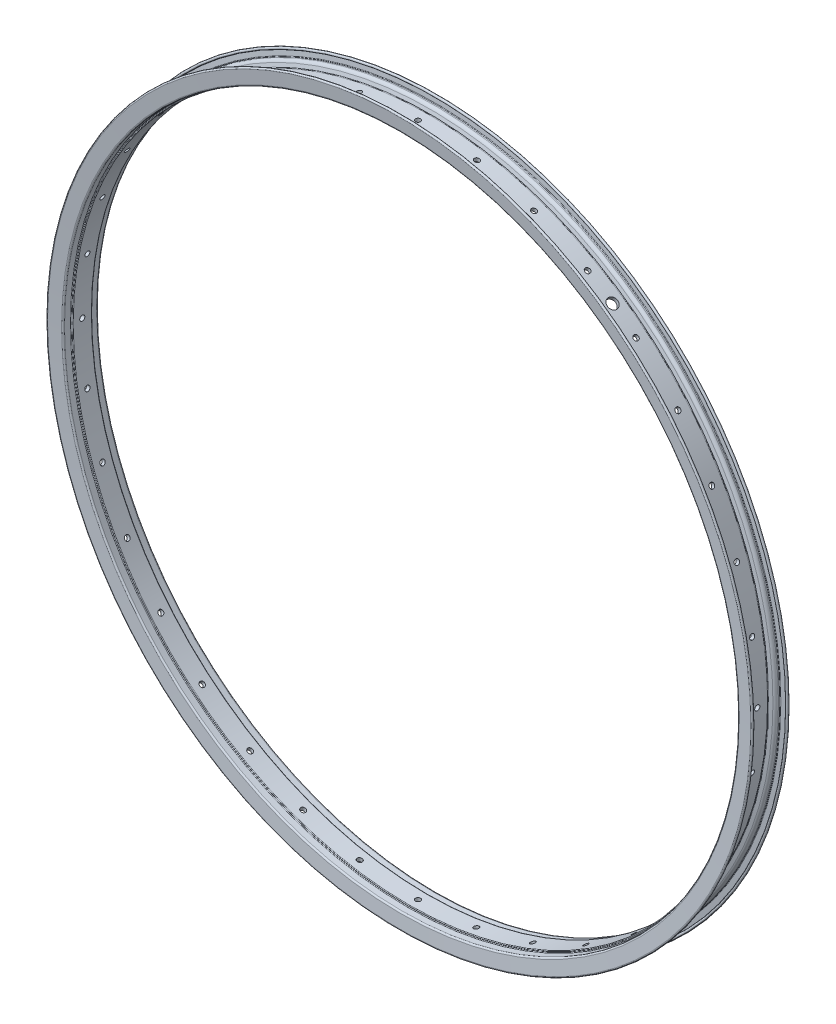
SolidWorks part; units mm, degrees
ref_plane "Alzado" through (0, 0, 0) normal (0, 0, 1) x (1, 0, 0)
ref_plane "Planta" through (0, 0, 0) normal (0, 1, 0) x (1, 0, 0)
ref_plane "Vista lateral" through (0, 0, 0) normal (1, 0, 0) x (0, 0, -1)
sketch "Croquis1" plane through (0, 0, 0) normal (1, 0, 0) x (0, 0, -1)
  line L0 (-255.6246, 0) -> (255.6246, 0) construction
  line L1 (0, 318.7713) -> (0, -318.7713) construction
  line L2 (7.3596, 274) -> (-7.3596, 274)
  line L3 (-7.8447, 274.6213) -> (-7.8053, 274.7787)
  line L4 (-8.2904, 275.4) -> (-13.1129, 275.4)
  line L5 (-14.3573, 276.5321) -> (-15.35, 287.0056)
  line L6 (-14.2601, 286.1045) -> (-13.8972, 282.2761)
  line L7 (-13.3995, 281.8233) -> (-12.3995, 281.8233)
  line L8 (-9.7847, 279.9251) -> (-8.9124, 277.2476)
  line L9 (-8.437, 276.9024) -> (8.437, 276.9024)
  line L10 (9.7847, 279.9251) -> (8.9124, 277.2476)
  line L11 (13.3995, 281.8233) -> (12.3995, 281.8233)
  line L12 (14.2601, 286.1045) -> (13.8972, 282.2761)
  line L13 (14.3573, 276.5321) -> (15.35, 287.0056)
  line L14 (8.2904, 275.4) -> (13.1129, 275.4)
  line L15 (7.8447, 274.6213) -> (7.8053, 274.7787)
  arc A1 (-14.2601, 286.1045) -> (-15.35, 287.0056) centre (-14.3545, 287.1) ccw
  arc A2 (-7.8053, 274.7787) -> (-8.2904, 275.4) centre (-8.2904, 274.9) ccw
  arc A3 (-7.8447, 274.6213) -> (-7.3596, 274) centre (-7.3596, 274.5) ccw
  arc A4 (-14.3573, 276.5321) -> (-13.1129, 275.4) centre (-13.1129, 276.65) ccw
  arc A5 (-9.7847, 279.9251) -> (-12.3995, 281.8233) centre (-12.3995, 279.0733) ccw
  arc A6 (-8.437, 276.9024) -> (-8.9124, 277.2476) centre (-8.437, 277.4024) cw
  arc A7 (-13.8972, 282.2761) -> (-13.3995, 281.8233) centre (-13.3995, 282.3233) ccw
  arc A8 (13.8972, 282.2761) -> (13.3995, 281.8233) centre (13.3995, 282.3233) cw
  arc A9 (8.437, 276.9024) -> (8.9124, 277.2476) centre (8.437, 277.4024) ccw
  arc A10 (9.7847, 279.9251) -> (12.3995, 281.8233) centre (12.3995, 279.0733) cw
  arc A11 (14.3573, 276.5321) -> (13.1129, 275.4) centre (13.1129, 276.65) cw
  arc A12 (7.8447, 274.6213) -> (7.3596, 274) centre (7.3596, 274.5) cw
  arc A13 (7.8053, 274.7787) -> (8.2904, 275.4) centre (8.2904, 274.9) cw
  arc A14 (14.2601, 286.1045) -> (15.35, 287.0056) centre (14.3545, 287.1) cw
  point P4 (0, 0)
  point P8 (0, 0)
  point P20 (-7.65, 275.4)
  point P23 (-8, 274)
  point P24 (-14.3545, 288.1)
  point P28 (-14.25, 275.4)
  point P33 (-8.8, 276.9024)
  point P37 (0, 274)
  point P38 (0, 276.9024)
  point P57 (8.8, 276.9024)
  point P58 (14.25, 275.4)
  point P59 (14.3545, 288.1)
  point P60 (8, 274)
  point P61 (7.65, 275.4)
  dimension "D4" = 12.7
  dimension "D3" = 14.1
  dimension "D7" = 0.5
  dimension "D8" = 2
  dimension "D13" = 1.25
  dimension "D14" = 2.75
  dimension "D15" = 0.5
  dimension "D1" = 8
  dimension "D2" = 14.25
  dimension "D5" = 548
  dimension "D6" = 6.6
  dimension "D9" = 1
  dimension "D10" = 8.8
  dimension "D11" = 10.7
  dimension "D12" = 30.7
  dimension "D16" = 1
  dimension "D17" = 14.9
revolve "Revolución1" add sketch "Croquis1" angle 360 about L0
sketch "Croquis2" plane through (0, 0, 0) normal (0, 1, 0) x (1, 0, 0)
  circle A0 centre (0, 0) radius 2.1
  dimension "D1" = 4.2
extrude "Cortar-Extruir1" cut sketch "Croquis2" against normal through all
pattern_circular "MatrizC1" count 36 over 360 about axis through (0, 0, -7.3596) along (0, 0, 1) of "Cortar-Extruir1"
sketch "Croquis3" plane through (0, 0, 0) normal (0, 0, 1) x (1, 0, 0)
  line L0 (0, 0) -> (136.6286, 240.8476)
  line L1 (0, 0) -> (179.593, 210.7636)
  line L2 (0, 0) -> (158.8247, 226.8252)
  arc A0 (179.593, 210.7636) -> (136.6286, 240.8476) centre (0, 0) ccw
ref_plane "Plano1" through (158.8247, 226.8252, 0) normal (0.5736, 0.8192, 0) x (0.8192, -0.5736, 0)
sketch "Croquis4" plane through (158.8247, 226.8252, 0) normal (0.5736, 0.8192, 0) x (0.8192, -0.5736, 0)
  circle A0 centre (0, 0) radius 4.2
  dimension "D1" = 8.4
extrude "Cortar-Extruir2" cut sketch "Croquis4" against normal up to next
